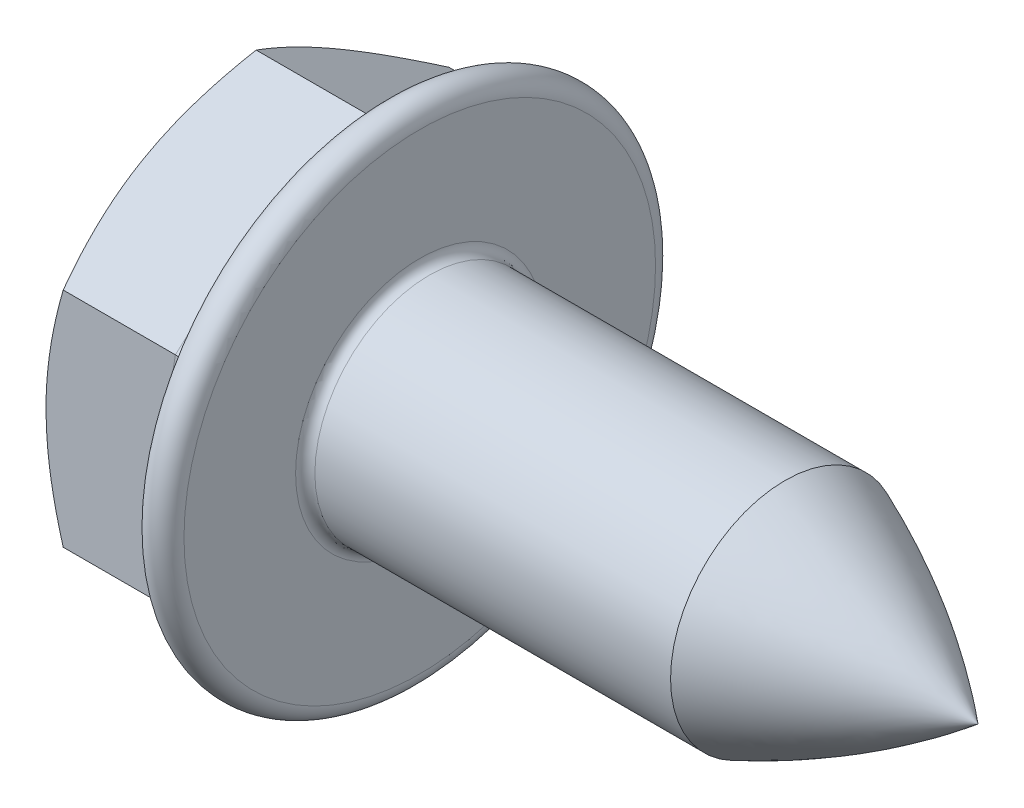
SolidWorks part; units mm, degrees
ref_plane "Front" through (0, 0, 0) normal (0, 0, 1) x (1, 0, 0)
ref_plane "Top" through (0, 0, 0) normal (0, 1, 0) x (1, 0, 0)
ref_plane "Right" through (0, 0, 0) normal (1, 0, 0) x (0, 0, -1)
sketch "Sketch2" plane through (0, 0, 0) normal (1, 0, 0) x (0, 0, -1)
  line L1 (0, 9.2376) -> (-8, 4.6188)
  line L2 (-8, 4.6188) -> (-8, -4.6188)
  line L3 (-8, -4.6188) -> (0, -9.2376)
  line L4 (0, -9.2376) -> (8, -4.6188)
  line L5 (8, -4.6188) -> (8, 4.6188)
  line L6 (8, 4.6188) -> (0, 9.2376)
  circle A0 centre (0, 0) radius 8 construction
extrude "BaseHead" add sketch "Sketch2" along normal blind 7.5
sketch "Sketch1" plane through (0, 0, 0) normal (0, 0, 1) x (1, 0, 0)
  line L0 (-9.5445, 0) -> (41.9665, 0) construction
  line L1 (30.65, 0) -> (30.65, 4.75)
  line L2 (30.65, 4.75) -> (7.5, 4.75)
  line L3 (7.5, 4.75) -> (7.5, 0)
  line L4 (30.65, 0) -> (7.5, 0)
  line L5 (7.5, 4.6188) -> (7.5, -4.6188) construction
  line L6 (9.6, 9.2774) -> (9.6, -3.0979) construction
  dimension "l" = 23.15
revolve "BaseBody" add sketch "Sketch1" angle 360 about L0
cosmetic thread "ThreadCosmetic1" [suppressed] parameters "D1"=21.05, "D2"=8.5
sketch "Sketch3" plane through (0, 0, 0) normal (0, 0, 1) x (1, 0, 0)
  line L0 (-1.5622, 0) -> (12.5659, 0) construction
  line L2 (7.5, 0) -> (7.5, 9.7782)
  line L3 (6.1, 10.0251) -> (2.4512, 0)
  line L4 (2.4512, 0) -> (7.5, 0)
  line L5 (7.5, 4.6188) -> (7.5, -4.6188) construction
  arc A0 (7.5, 9.7782) -> (6.1, 10.0251) centre (6.7782, 9.7782) ccw
  dimension "dc" = 21
  dimension "D2" = 70
  dimension "c" = 1.4
revolve "Neck" add sketch "Sketch3" angle 360 about L0
sketch "Sketch4" plane through (0, 0, 0) normal (0, 0, 1) x (1, 0, 0)
  line L0 (10.6638, 0) -> (-1.5125, 0) construction
  line L2 (0, 8) -> (0.7145, 9.2376)
  line L5 (0.7145, 9.2376) -> (0, 9.2376)
  line L6 (0, 9.2376) -> (0, 8)
  dimension "D1" = 16
  dimension "D2" = 30
revolve "Cut-Revolve7" cut sketch "Sketch4" angle 360 about L0
fillet "Fillet1" radius 0.4 1 edges at (7.5, 0, 4.75)
fillet "Fillet2" radius 0.6 6 edges
sketch "Sketch5" plane through (0, 0, 0) normal (0, 0, 1) x (1, 0, 0)
  line L0 (31.9782, 0) -> (17.0112, 0) construction
  line L2 (26.45, -4.75) -> (28.55, -4.75)
  line L3 (28.55, -4.75) -> (30.65, -4.225)
  line L5 (30.65, -4.75) -> (30.65, 4.75) construction
  line L6 (26.45, -4.75) -> (26.45, -5.25)
  line L7 (26.45, -5.25) -> (30.65, -5.25)
  line L8 (30.65, -5.25) -> (30.65, -4.225)
  point P15 (28.55, -4.75)
  dimension "D2" = 2.1
  dimension "D4" = 0.5
  dimension "D1" = 9.5
  dimension "D3" = 0.525
revolve "Cut-Revolve1" cut sketch "Sketch5" angle 360 about L0
sketch "Sketch6" plane through (0, 0, 0) normal (0, 0, 1) x (1, 0, 0)
  line L0 (33.3907, 0) -> (10.0621, 0) construction
  line L2 (30.65, -4.75) -> (30.65, 4.75) construction
  line L3 (30.65, 0) -> (22.65, -4.75) construction
  line L6 (30.65, 0) -> (31.15, 0)
  line L7 (22.65, -4.75) -> (30.65, -4.75)
  line L8 (31.15, 0) -> (31.15, -4.75)
  line L9 (31.15, -4.75) -> (30.65, -4.75)
  arc A0 (30.65, 0) -> (22.65, -4.75) centre (10.4863, 24.8481) cw
  dimension "D1" = 32
  dimension "D3" = 9.5
  dimension "D2" = 0.5
revolve "Cut-Revolve6" cut sketch "Sketch6" angle 360 about L0
sketch "Sketch7" plane through (0, 0, 0) normal (0, 0, 1) x (1, 0, 0)
  line L0 (0, 0) -> (-5.0817, 0) construction
  line L1 (-0.5, 6.6667) -> (1.0417, 6.6667)
  line L2 (-0.5, 6.6667) -> (-0.5, 0)
  line L3 (-0.5, 0) -> (1.25, 0)
  line L4 (1.25, 6.4583) -> (1.25, 0)
  arc A0 (1.0417, 6.6667) -> (1.25, 6.4583) centre (1.0417, 6.4583) cw
  point P9 (1.25, 6.6667)
  dimension "D4" = 0.2083
  dimension "D1" = 0.5
  dimension "D2" = 1.25
  dimension "D3" = 13.3333
revolve "Cut-Revolve8" cut sketch "Sketch7" angle 360 about L0
sketch "Sketch8" plane through (0, 0, 0) normal (0, 0, 1) x (1, 0, 0)
  line L0 (9.35, 5.25) -> (9.85, 5.25)
  line L1 (9.85, 5.25) -> (9.85, 4.75)
  line L2 (9.85, 4.75) -> (9.6, 4.317)
  line L3 (9.6, 4.317) -> (9.35, 4.75)
  line L4 (9.35, 4.75) -> (9.35, 5.25)
  line L5 (0, 0) -> (-6.1497, 0) construction
  line L6 (7.5, -9.7782) -> (7.5, 9.7782) construction
  dimension "D1" = 9.5
  dimension "D2" = 0.5
  dimension "D3" = 2.1
revolve "Cut-Revolve10" [suppressed] cut sketch "Sketch8" angle 360 about L5
pattern_linear "LPattern10" [suppressed] count 35 spacing 0.6 along (1, 0, 0) of bodies 108
equation "\"D3@Sketch5\" = \"yf@Sketch5\" / 8"
equation "\"D2@ThreadCosmetic1\" = \"st@Sketch1\" - 1"
equation "\"D1@Sketch6\" = \"yc@Sketch6\" * 4"
equation "\"D3@Sketch6\" = \"st@Sketch1\""
equation "\"D2@Sketch5\" = \"yf@Sketch5\" / 2"
equation "\"D1@Sketch4\" = \"s@Sketch2\""
equation "\"D1@Sketch5\" = \"st@Sketch1\""
equation "\"D1@ThreadCosmetic1\" = \"l@Sketch1\" - \"a@Sketch1\""
equation "\"D2@Sketch7\" = \"k@BaseHead\" / 6"
equation "\"D3@Sketch7\" = \"s@Sketch2\" * 5 / 6"
equation "\"D4@Sketch7\" = \"D2@Sketch7\" / 6"
equation "\"D1@Sketch8\" = \"st@Sketch1\""
equation "\"D2@Sketch8\" = (  \"st@Sketch1\" - \"D2@ThreadCosmetic1\" )  / 2"
equation "\"D3@Sketch8\" = \"a@Sketch1\""
equation "\"D3@LPattern10\" = \"D2@Sketch8\" * 1.2"
equation "\"D1@LPattern10\" = \"D1@ThreadCosmetic1\" / \"D3@LPattern10\""
